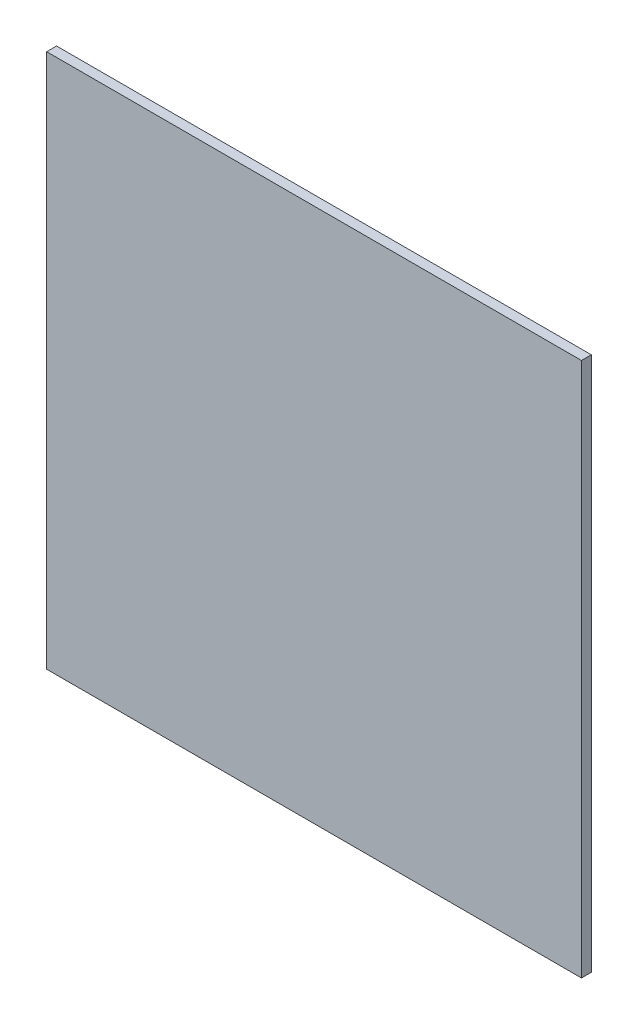
SolidWorks part; units mm, degrees
material "6061-T6 (SS)"
ref_plane "Front Plane" through (0, 0, 0) normal (0, 0, 1) x (1, 0, 0)
ref_plane "Top Plane" through (0, 0, 0) normal (0, 1, 0) x (1, 0, 0)
ref_plane "Right Plane" through (0, 0, 0) normal (1, 0, 0) x (0, 0, -1)
sketch "Sketch1" plane through (0, 0, 0) normal (0, 0, 1) x (1, 0, 0)
  line L1 (-325, -325) -> (325, -325)
  line L2 (-325, -325) -> (-325, 325)
  line L3 (-325, 325) -> (325, 325)
  line L4 (325, -325) -> (325, 325)
extrude "Bench_Plate" add sketch "Sketch1" along normal blind 12
